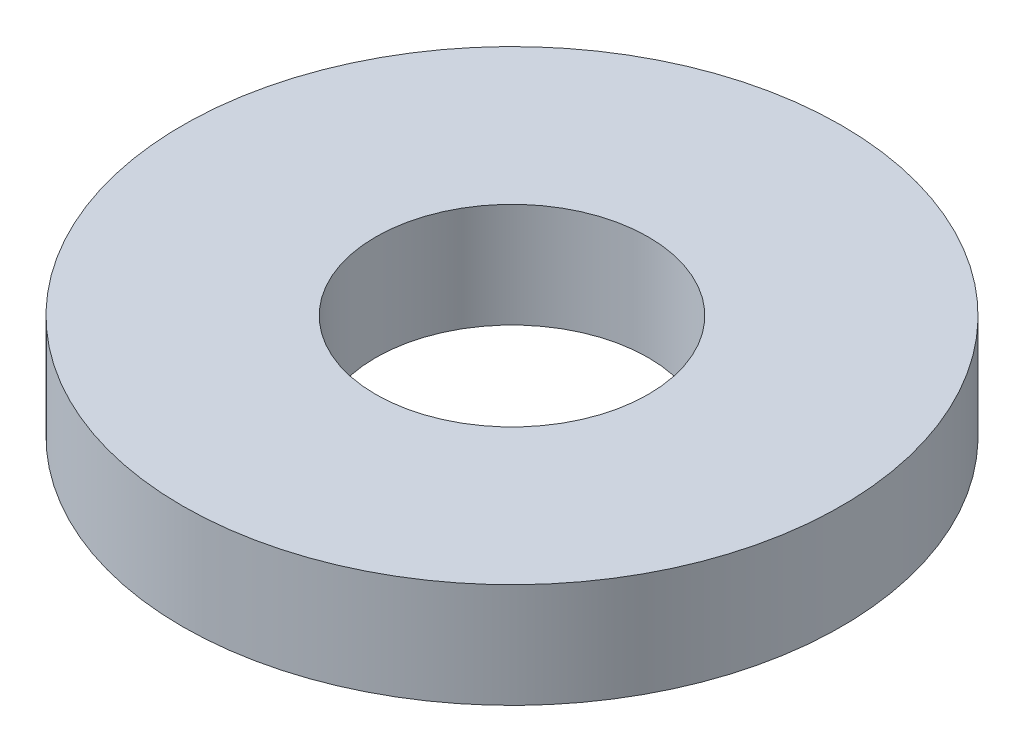
SolidWorks part; units mm, degrees
ref_plane "Front Plane" through (0, 0, 0) normal (0, 0, 1) x (1, 0, 0)
ref_plane "Top Plane" through (0, 0, 0) normal (0, 1, 0) x (1, 0, 0)
ref_plane "Right Plane" through (0, 0, 0) normal (1, 0, 0) x (0, 0, -1)
sketch "Sketch1" plane through (0, 0, 0) normal (0, 1, 0) x (1, 0, 0)
  circle A0 centre (0, 0) radius 72.5
  dimension "FLANGE_OD" = 145
extrude "Boss-Extrude1" add sketch "Sketch1" along normal blind 23
sketch "Sketch2" plane through (0, 0, 0) normal (0, 1, 0) x (1, 0, 0)
  circle A0 centre (0, 0) radius 30
  dimension "BORE_D" = 60
extrude "Cut-Extrude1" cut sketch "Sketch2" along normal through all
sketch "Sketch3" plane through (0, 23, 0) normal (0, 1, 0) x (1, 0, 0)
  circle A0 centre (0, 0) radius 23.8137 construction
  circle A1 centre (-23.8137, 0) radius 2.9091
  dimension "BOLT_D" = 5.8182
  dimension "BOLT_PCD" = 47.6275
extrude "Cut-Extrude2" cut sketch "Sketch3" against normal blind 14.4944 rebuild error yes
pattern_circular "CirPattern1" count 4 over 360 rebuild error yes
